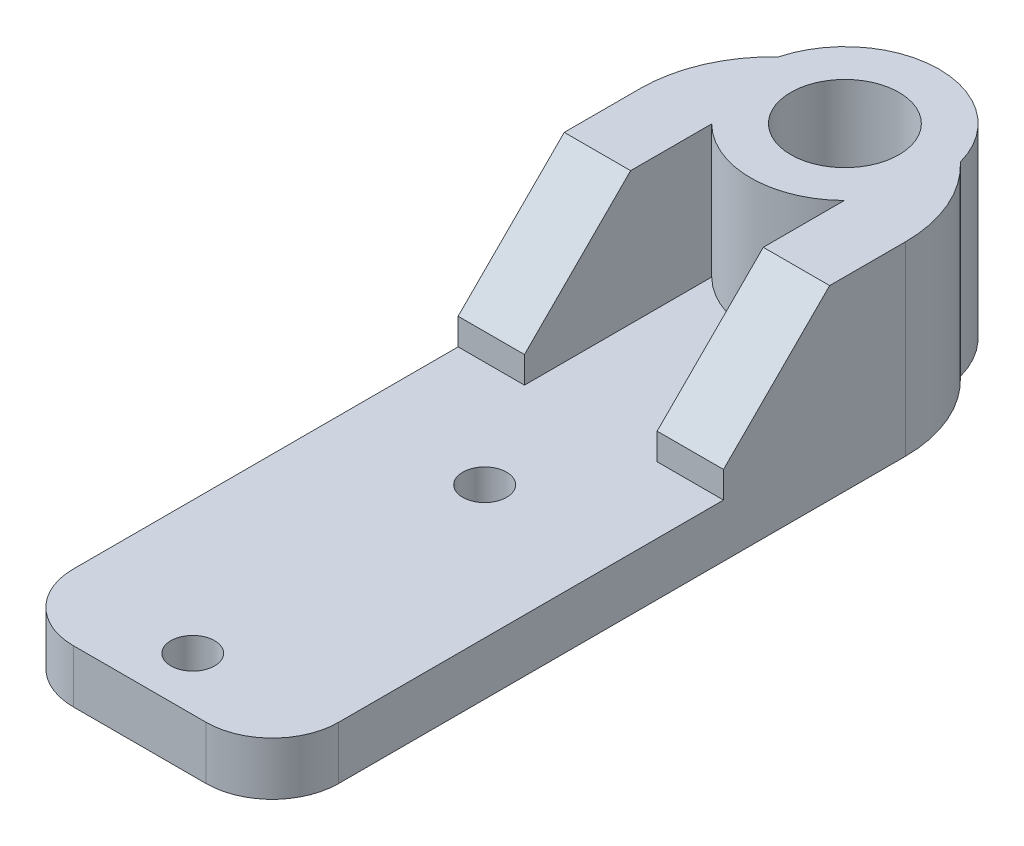
SolidWorks part; units mm, degrees
ref_plane "Front Plane" through (0, 0, 0) normal (0, 0, 1) x (1, 0, 0)
ref_plane "Top Plane" through (0, 0, 0) normal (0, 1, 0) x (1, 0, 0)
ref_plane "Right Plane" through (0, 0, 0) normal (1, 0, 0) x (0, 0, -1)
sketch "Sketch1" plane through (0, 0, 0) normal (0, 1, 0) x (1, 0, 0)
  line L1 (-10, -27.5) -> (10, -27.5)
  line L2 (-10, -27.5) -> (-10, 27.5)
  line L3 (-10, 27.5) -> (10, 27.5)
  line L4 (10, -27.5) -> (10, 27.5)
  line L5 (-10, -27.5) -> (10, 27.5) construction
  line L6 (-10, 27.5) -> (10, -27.5) construction
  point P0 (0, 0)
  dimension "D1" = 55
  dimension "D2" = 20
extrude "Boss-Extrude1" add sketch "Sketch1" along normal blind 4
sketch "Sketch2" plane through (0, 4, 0) normal (0, 1, 0) x (1, 0, 0)
  line L0 (0, 27.5) -> (0, 25.65) construction
  line L1 (10, 27.5) -> (-10, 27.5) construction
  line L2 (-10, -27.5) -> (10, -27.5) construction
  circle A0 centre (0, 25.65) radius 4.075
  dimension "D1" = 8.15
  dimension "D2" = 53.15
extrude "Cut-Extrude1" cut sketch "Sketch2" against normal through all both and the other way through all
sketch "Sketch3" plane through (0, 4, 0) normal (0, 1, 0) x (1, 0, 0)
  circle A0 centre (0, 25.65) radius 7.1
  circle A1 centre (0, 25.65) radius 4.075 construction
  circle A2 centre (0, 25.65) radius 4.075
  dimension "D1" = 14.2
extrude "Boss-Extrude2" add sketch "Sketch3" along normal blind 10 and the other way up to surface (4 mm away) other way up to face at (0, 0, -8.1792)
sketch "Sketch4" plane through (10, 0, 0) normal (1, 0, 0) x (0, 0, -1)
  line L0 (32.75, 14) -> (18.55, 14) construction
  line L1 (27.5, 0) -> (6.5, 0)
  line L2 (27.5, 0) -> (27.5, 14)
  line L3 (27.5, 14) -> (6.5, 14)
  line L4 (6.5, 0) -> (6.5, 14)
  dimension "D1" = 21
extrude "Boss-Extrude3" add sketch "Sketch4" against normal blind 5
chamfer "Chamfer1" distance 8 angle 45 1 edges at (7.5, 14, -6.5)
mirror "Mirror1" about plane through (0, 0, 0) normal (1, 0, 0) of "Boss-Extrude3", "Chamfer1"
fillet "Fillet3" radius 10 2 edges at (10, 7, -27.5) (-10, 7, -27.5)
fillet "Fillet4" radius 5 2 edges at (10, 2, 27.5) (-10, 2, 27.5)
sketch "Sketch5" plane through (0, 4, 0) normal (0, 1, 0) x (1, 0, 0)
  line L0 (0, -27.5) -> (0, -1.5) construction
  line L1 (-5, -27.5) -> (5, -27.5) construction
  circle A0 centre (0, -23.5) radius 1.65
  circle A1 centre (0, -1.5) radius 1.65
  dimension "D2" = 3.3
  dimension "D1" = 4
  dimension "D3" = 22
extrude "Cut-Extrude2" cut sketch "Sketch5" against normal through all
